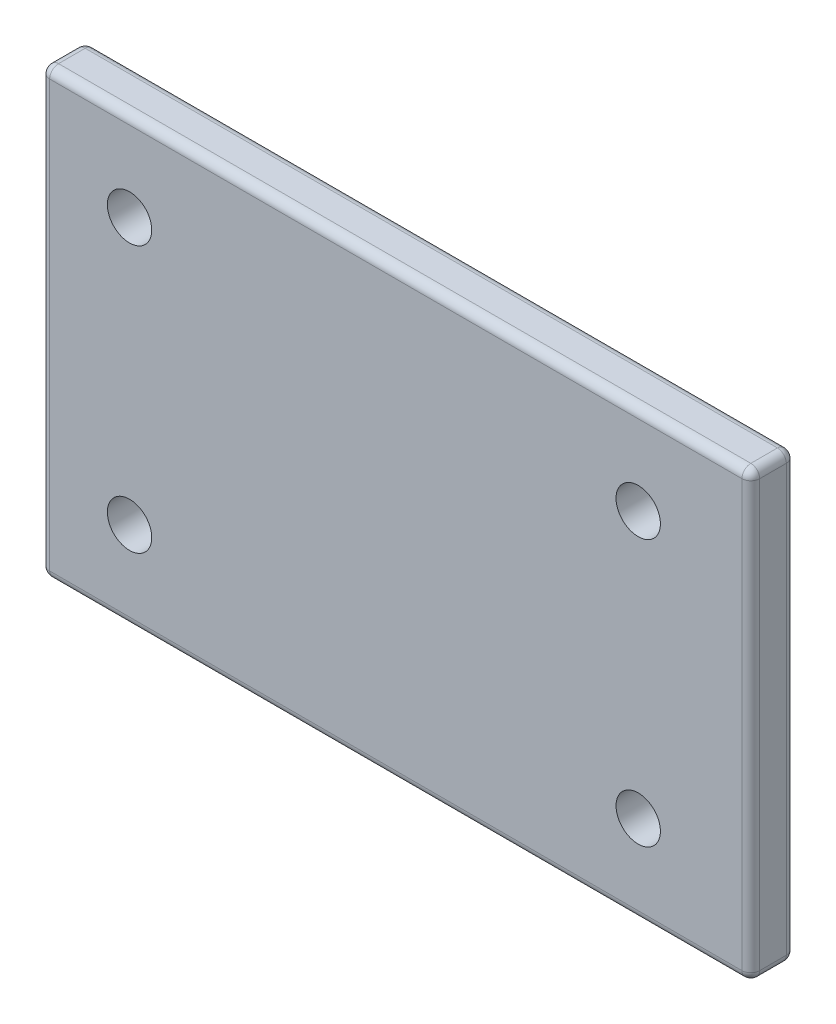
SolidWorks part; units mm, degrees
ref_plane "Front Plane" through (0, 0, 0) normal (0, 0, 1) x (1, 0, 0)
ref_plane "Top Plane" through (0, 0, 0) normal (0, 1, 0) x (1, 0, 0)
ref_plane "Right Plane" through (0, 0, 0) normal (1, 0, 0) x (0, 0, -1)
sketch "Sketch1" plane through (0, 0, 0) normal (0, 0, 1) x (1, 0, 0)
  line L1 (80, -50) -> (-80, -50)
  line L2 (80, -50) -> (80, 50)
  line L3 (80, 50) -> (-80, 50)
  line L4 (-80, -50) -> (-80, 50)
  line L5 (80, -50) -> (-80, 50) construction
  line L6 (80, 50) -> (-80, -50) construction
  point P0 (0, 0)
  dimension "D1" = 160
  dimension "D2" = 100
extrude "Boss-Extrude2" add sketch "Sketch1" along normal blind 10
sketch "Sketch2" plane through (0, 0, 10) normal (0, 0, 1) x (1, 0, 0)
  line L0 (-2.6876, 0) -> (-2.6876, 52.2639) construction
  line L1 (-2.6876, 0) -> (54.2486, 0) construction
  line L2 (-80, -50) -> (80, -50) construction
  line L3 (80, 50) -> (-80, 50) construction
  line L4 (-80, 50) -> (-80, -50) construction
  circle A0 centre (-60, 30) radius 5
  circle A1 centre (54.6248, 30) radius 5
  circle A2 centre (54.6248, -30) radius 5
  circle A3 centre (-60, -30) radius 5
  point P15 (0, 0)
  point P16 (0, 0)
  point P17 (-80, 28.0339)
  point P20 (0, 0)
  point P21 (0, 0)
  dimension "D1" = 20
  dimension "D2" = 20
  dimension "D3" = 20
extrude "Cut-Extrude1" cut sketch "Sketch2" against normal blind 10
fillet "Fillet3" radius 2 3 edges at (0, 50, 10) (-80, 50, 5) (-80, 0, 10)
fillet "Fillet4" radius 2 4 edges at (80, 49.4142, 9.4142) (80, 0, 0) (80, 50, 4) (80, -1, 10)
fillet "Fillet5" radius 2 7 edges at (-80, -50, 4) (-79.4142, -50, 9.4142) (79.4142, -50, 0.5858) (79.4142, -50, 9.4142) (-1, -50, 0) (80, -50, 5) (0, -50, 10)
fillet "Fillet6" radius 2 5 edges at (79.4142, 49.4142, 0.5858) (0, 50, 0) (-79.4142, 49.4142, 0) (-79.4142, -49.4142, 0.5858) (-80, 0, 0)
